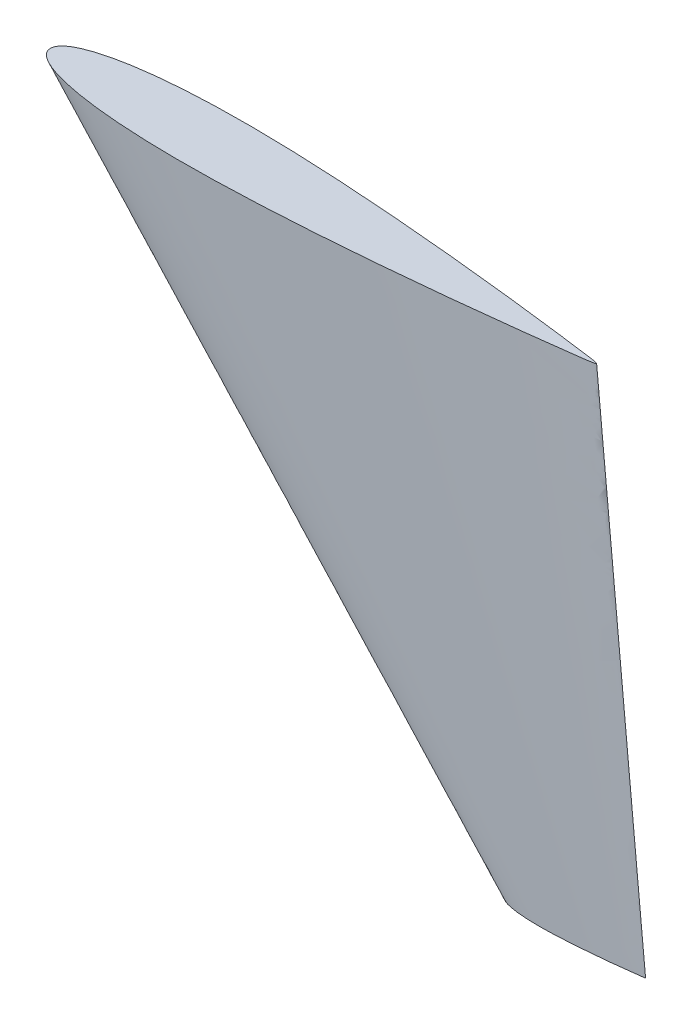
SolidWorks part; units mm, degrees
ref_plane "Front Plane" through (0, 0, 0) normal (0, 0, 1) x (1, 0, 0)
ref_plane "Top Plane" through (0, 0, 0) normal (0, 1, 0) x (1, 0, 0)
ref_plane "Right Plane" through (0, 0, 0) normal (1, 0, 0) x (0, 0, -1)
curve "Curve1"
  spline degree 3 poles (989.1889, 0, -3.124) (1003.9656, 0, 0) (989.1889, 0, 3.124) (979.4957, 0, 3.9602) (962.3964, 0, 6.4841) (943.9428, 0, 8.8491) (922.9132, 0, 11.6051) (900.2887, 0, 14.4478) (876.1894, 0, 17.4113) (850.9063, 0, 20.4351) (824.6249, 0, 23.4743) (797.5193, 0, 26.5234) (769.735, 0, 29.5334) (741.4059, 0, 32.5134) (712.6526, 0, 35.4198) (683.5857, 0, 38.2366) (654.3085, 0, 40.9505) (624.9168, 0, 43.5692) (595.4919, 0, 46.0176) (566.1196, 0, 48.3457) (536.8752, 0, 50.4873) (507.8364, 0, 52.4785) (479.0688, 0, 54.2437) (450.6418, 0, 55.8057) (422.6181, 0, 57.149) (395.0577, 0, 58.2561) (368.0197, 0, 59.0905) (341.5624, 0, 59.6944) (315.7376, 0, 59.999) (290.5993, 0, 60.0553) (266.1976, 0, 59.7899) (242.5818, 0, 59.2641) (219.7995, 0, 58.4267) (197.8965, 0, 57.3046) (176.9228, 0, 55.8955) (156.9193, 0, 54.1908) (137.9264, 0, 52.2182) (119.9888, 0, 49.9445) (103.1457, 0, 47.4173) (87.4377, 0, 44.6503) (72.9094, 0, 41.6113) (59.5881, 0, 38.3545) (47.5124, 0, 34.8789) (36.7185, 0, 31.1996) (27.2445, 0, 27.3184) (19.1092, 0, 23.264) (12.343, 0, 19.027) (6.9689, 0, 14.6049) (3.0199, 0, 9.972) (0.5665, 0, 5.0849) (-0.2745, 0, 0) (0.5665, 0, -5.0849) (3.0199, 0, -9.972) (6.9689, 0, -14.6049) (12.343, 0, -19.027) (19.1092, 0, -23.264) (27.2445, 0, -27.3184) (36.7185, 0, -31.1996) (47.5124, 0, -34.8789) (59.5881, 0, -38.3545) (72.9094, 0, -41.6113) (87.4377, 0, -44.6503) (103.1457, 0, -47.4173) (119.9888, 0, -49.9445) (137.9264, 0, -52.2182) (156.9193, 0, -54.1908) (176.9228, 0, -55.8955) (197.8965, 0, -57.3046) (219.7995, 0, -58.4267) (242.5818, 0, -59.2641) (266.1976, 0, -59.7899) (290.5993, 0, -60.0553) (315.7376, 0, -59.999) (341.5624, 0, -59.6944) (368.0197, 0, -59.0905) (395.0577, 0, -58.2561) (422.6181, 0, -57.149) (450.6418, 0, -55.8057) (479.0688, 0, -54.2437) (507.8364, 0, -52.4785) (536.8752, 0, -50.4873) (566.1196, 0, -48.3457) (595.4919, 0, -46.0176) (624.9168, 0, -43.5692) (654.3085, 0, -40.9505) (683.5857, 0, -38.2366) (712.6526, 0, -35.4198) (741.4059, 0, -32.5134) (769.735, 0, -29.5334) (797.5193, 0, -26.5234) (824.6249, 0, -23.4743) (850.9063, 0, -20.4351) (876.1894, 0, -17.4113) (900.2887, 0, -14.4478) (922.9132, 0, -11.6051) (943.9428, 0, -8.8491) (962.3964, 0, -6.4841) (979.4957, 0, -3.9602) (989.1889, 0, -3.124) (1003.9656, 0, 0) (989.1889, 0, 3.124) knots -0.01819 -0.010091 -0.003701 0 0.003701 0.010091 0.01819 0.027571 0.037978 0.04922 0.061159 0.073676 0.086676 0.10007 0.113795 0.12778 0.141967 0.156301 0.170733 0.185213 0.199702 0.214161 0.22855 0.24283 0.256971 0.270941 0.284704 0.298236 0.311509 0.32449 0.337159 0.349495 0.361463 0.373051 0.384237 0.394993 0.405307 0.415153 0.424519 0.43339 0.441745 0.449568 0.456846 0.463572 0.469733 0.475323 0.480337 0.484781 0.488676 0.492055 0.49498 0.497567 0.5 0.502433 0.50502 0.507945 0.511324 0.515219 0.519663 0.524677 0.530267 0.536428 0.543154 0.550432 0.558255 0.56661 0.575481 0.584847 0.594693 0.605007 0.615763 0.626949 0.638537 0.650505 0.662841 0.67551 0.688491 0.701764 0.715296 0.729059 0.743029 0.75717 0.77145 0.785839 0.800298 0.814787 0.829267 0.843699 0.858033 0.87222 0.886205 0.89993 0.913324 0.926324 0.938841 0.95078 0.962022 0.972429 0.98181 0.989909 0.996299 1 1.003701 1.010091 1.01819 periodic
sketch "Sketch2" plane through (0, 0, 0) normal (0, 1, 0) x (1, 0, 0)
  line L0 (7800, 0) -> (0, 0) construction
  line L1 (0, 0) -> (0, 395.0757) construction
  spline S1 degree 3 poles (7715.6733, -24.367) (7830.9313, 0) (7715.6733, 24.367) (7640.0665, 30.8898) (7506.6921, 50.5762) (7362.7536, 69.0228) (7198.7231, 90.52) (7022.252, 112.6929) (6834.2776, 135.808) (6637.0694, 159.3941) (6432.074, 183.0993) (6220.6504, 206.8827) (6003.9328, 230.3604) (5782.9657, 253.6049) (5558.6901, 276.2741) (5331.9683, 298.2455) (5103.6066, 319.4138) (4874.3512, 339.8394) (4644.8367, 358.9371) (4415.733, 377.0965) (4187.6269, 393.8012) (3961.1239, 409.3322) (3736.7364, 423.1006) (3515.0057, 435.2847) (3296.4215, 445.7625) (3081.4499, 454.3974) (2870.5539, 460.9058) (2664.1865, 465.6165) (2462.7531, 467.9925) (2266.6747, 468.431) (2076.3415, 466.3609) (1892.1383, 462.2603) (1714.4358, 455.7279) (1543.593, 446.9762) (1379.9976, 435.9846) (1223.9703, 422.6886) (1075.8258, 407.3018) (935.9126, 389.5669) (804.5364, 369.855) (682.0138, 348.2726) (568.693, 324.5681) (464.7869, 299.1653) (370.5968, 272.0553) (286.404, 243.3569) (212.5068, 213.0831) (149.052, 181.4593) (96.2758, 148.4109) (54.3577, 113.9185) (23.5554, 77.7814) (4.4187, 39.662) (-2.1412, 0) (4.4187, -39.662) (23.5554, -77.7814) (54.3577, -113.9185) (96.2758, -148.4109) (149.052, -181.4593) (212.5068, -213.0831) (286.404, -243.3569) (370.5968, -272.0553) (464.7869, -299.1653) (568.693, -324.5681) (682.0138, -348.2726) (804.5364, -369.855) (935.9126, -389.5669) (1075.8258, -407.3018) (1223.9703, -422.6886) (1379.9976, -435.9846) (1543.593, -446.9762) (1714.4358, -455.7279) (1892.1383, -462.2603) (2076.3415, -466.3609) (2266.6747, -468.431) (2462.7531, -467.9925) (2664.1865, -465.6165) (2870.5539, -460.9058) (3081.4499, -454.3974) (3296.4215, -445.7625) (3515.0057, -435.2847) (3736.7364, -423.1006) (3961.1239, -409.3322) (4187.6269, -393.8012) (4415.733, -377.0965) (4644.8367, -358.9371) (4874.3512, -339.8394) (5103.6066, -319.4138) (5331.9683, -298.2455) (5558.6901, -276.2741) (5782.9657, -253.6049) (6003.9328, -230.3604) (6220.6504, -206.8827) (6432.074, -183.0993) (6637.0694, -159.3941) (6834.2776, -135.808) (7022.252, -112.6929) (7198.7231, -90.52) (7362.7536, -69.0228) (7506.6921, -50.5762) (7640.0665, -30.8898) (7715.6733, -24.367) (7830.9313, 0) (7715.6733, 24.367) knots -0.01819 -0.010091 -0.003701 0 0.003701 0.010091 0.01819 0.027571 0.037978 0.04922 0.061159 0.073676 0.086676 0.10007 0.113795 0.12778 0.141967 0.156301 0.170733 0.185213 0.199702 0.214161 0.22855 0.24283 0.256971 0.270941 0.284704 0.298236 0.311509 0.32449 0.337159 0.349495 0.361463 0.373051 0.384237 0.394993 0.405307 0.415153 0.424519 0.43339 0.441745 0.449568 0.456846 0.463572 0.469733 0.475323 0.480337 0.484781 0.488676 0.492055 0.49498 0.497567 0.5 0.502433 0.50502 0.507945 0.511324 0.515219 0.519663 0.524677 0.530267 0.536428 0.543154 0.550432 0.558255 0.56661 0.575481 0.584847 0.594693 0.605007 0.615763 0.626949 0.638537 0.650505 0.662841 0.67551 0.688491 0.701764 0.715296 0.729059 0.743029 0.75717 0.77145 0.785839 0.800298 0.814787 0.829267 0.843699 0.858033 0.87222 0.886205 0.89993 0.913324 0.926324 0.938841 0.95078 0.962022 0.972429 0.98181 0.989909 0.996299 1 1.003701 1.010091 1.01819 only from (7800, 0) to (7800, 0)
  point P1 (0, 0)
  point P4 (0, 0)
  dimension "D1" = 7800
ref_plane "Plane1" through (0, -7250, 0) normal (0, 1, 0) x (1, 0, 0)
sketch "Sketch6" plane through (0, -7250, 0) normal (0, 1, 0) x (1, 0, 0)
  line L0 (8500, 0) -> (6500, 0) construction
  line L1 (6500, 0) -> (6500, 213.2137) construction
  line L2 (7800, 0) -> (0, 0) construction
  spline S1 degree 3 poles (8478.3778, -6.2479) (8507.9311, 0) (8478.3778, 6.2479) (8458.9914, 7.9205) (8424.7929, 12.9683) (8387.8855, 17.6982) (8345.8264, 23.2103) (8300.5774, 28.8956) (8252.3789, 34.8226) (8201.8127, 40.8703) (8149.2497, 46.9485) (8095.0386, 53.0469) (8039.4699, 59.0668) (7982.8117, 65.0269) (7925.3052, 70.8395) (7867.1714, 76.4732) (7808.6171, 81.901) (7749.8336, 87.1383) (7690.9838, 92.0352) (7632.2392, 96.6914) (7573.7505, 100.9747) (7515.6728, 104.957) (7458.1376, 108.4873) (7401.2835, 111.6115) (7345.2363, 114.2981) (7290.1154, 116.5121) (7236.0395, 118.181) (7183.1248, 119.3888) (7131.4752, 119.9981) (7081.1987, 120.1105) (7032.3952, 119.5797) (6985.1637, 118.5283) (6939.5989, 116.8533) (6895.7931, 114.6093) (6853.8455, 111.7909) (6813.8385, 108.3817) (6775.8528, 104.4364) (6739.9776, 99.889) (6706.2914, 94.8346) (6674.8753, 89.3007) (6645.8187, 83.2226) (6619.1761, 76.709) (6595.0248, 69.7578) (6573.4369, 62.3992) (6554.4889, 54.6367) (6538.2185, 46.528) (6524.6861, 38.0541) (6513.9379, 29.2099) (6506.0399, 19.9439) (6501.133, 10.1697) (6499.451, 0) (6501.133, -10.1697) (6506.0399, -19.9439) (6513.9379, -29.2099) (6524.6861, -38.0541) (6538.2185, -46.528) (6554.4889, -54.6367) (6573.4369, -62.3992) (6595.0248, -69.7578) (6619.1761, -76.709) (6645.8187, -83.2226) (6674.8753, -89.3007) (6706.2914, -94.8346) (6739.9776, -99.889) (6775.8528, -104.4364) (6813.8385, -108.3817) (6853.8455, -111.7909) (6895.7931, -114.6093) (6939.5989, -116.8533) (6985.1637, -118.5283) (7032.3952, -119.5797) (7081.1987, -120.1105) (7131.4752, -119.9981) (7183.1248, -119.3888) (7236.0395, -118.181) (7290.1154, -116.5121) (7345.2363, -114.2981) (7401.2835, -111.6115) (7458.1376, -108.4873) (7515.6728, -104.957) (7573.7505, -100.9747) (7632.2392, -96.6914) (7690.9838, -92.0352) (7749.8336, -87.1383) (7808.6171, -81.901) (7867.1714, -76.4732) (7925.3052, -70.8395) (7982.8117, -65.0269) (8039.4699, -59.0668) (8095.0386, -53.0469) (8149.2497, -46.9485) (8201.8127, -40.8703) (8252.3789, -34.8226) (8300.5774, -28.8956) (8345.8264, -23.2103) (8387.8855, -17.6982) (8424.7929, -12.9683) (8458.9914, -7.9205) (8478.3778, -6.2479) (8507.9311, 0) (8478.3778, 6.2479) knots -0.01819 -0.010091 -0.003701 0 0.003701 0.010091 0.01819 0.027571 0.037978 0.04922 0.061159 0.073676 0.086676 0.10007 0.113795 0.12778 0.141967 0.156301 0.170733 0.185213 0.199702 0.214161 0.22855 0.24283 0.256971 0.270941 0.284704 0.298236 0.311509 0.32449 0.337159 0.349495 0.361463 0.373051 0.384237 0.394993 0.405307 0.415153 0.424519 0.43339 0.441745 0.449568 0.456846 0.463572 0.469733 0.475323 0.480337 0.484781 0.488676 0.492055 0.49498 0.497567 0.5 0.502433 0.50502 0.507945 0.511324 0.515219 0.519663 0.524677 0.530267 0.536428 0.543154 0.550432 0.558255 0.56661 0.575481 0.584847 0.594693 0.605007 0.615763 0.626949 0.638537 0.650505 0.662841 0.67551 0.688491 0.701764 0.715296 0.729059 0.743029 0.75717 0.77145 0.785839 0.800298 0.814787 0.829267 0.843699 0.858033 0.87222 0.886205 0.89993 0.913324 0.926324 0.938841 0.95078 0.962022 0.972429 0.98181 0.989909 0.996299 1 1.003701 1.010091 1.01819 only from (8500, 0) to (8500, 0)
  point P1 (6500, 0)
  dimension "D1" = 2000
  dimension "D2" = 6500
loft "Loft2" add profiles "Sketch6", "Sketch2" connector at (8499.9828, -7250, -0.1359) connector at (7799.7348, 0, -1.0598)
